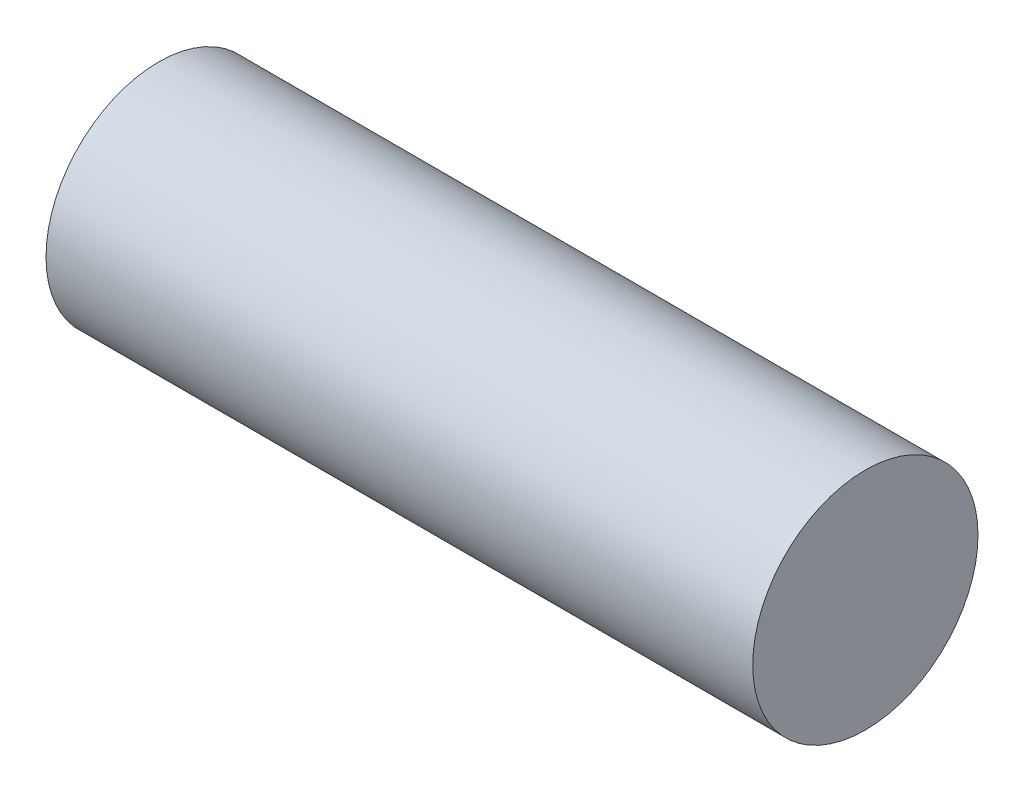
SolidWorks part; units mm, degrees
ref_plane "Front Plane" through (0, 0, 0) normal (0, 0, 1) x (1, 0, 0)
ref_plane "Top Plane" through (0, 0, 0) normal (0, 1, 0) x (1, 0, 0)
ref_plane "Right Plane" through (0, 0, 0) normal (1, 0, 0) x (0, 0, -1)
sketch "Sketch2" plane through (0, 0, 0) normal (0, 1, 0) x (1, 0, 0)
  line L0 (0, 0) -> (400, 0)
  line L1 (400, 0) -> (400, 63.75)
  line L2 (400, 63.75) -> (0, 63.75)
  line L3 (0, 63.75) -> (0, 0)
revolve "Revolve1" add sketch "Sketch2" angle 360 about L2 reverse direction yes
